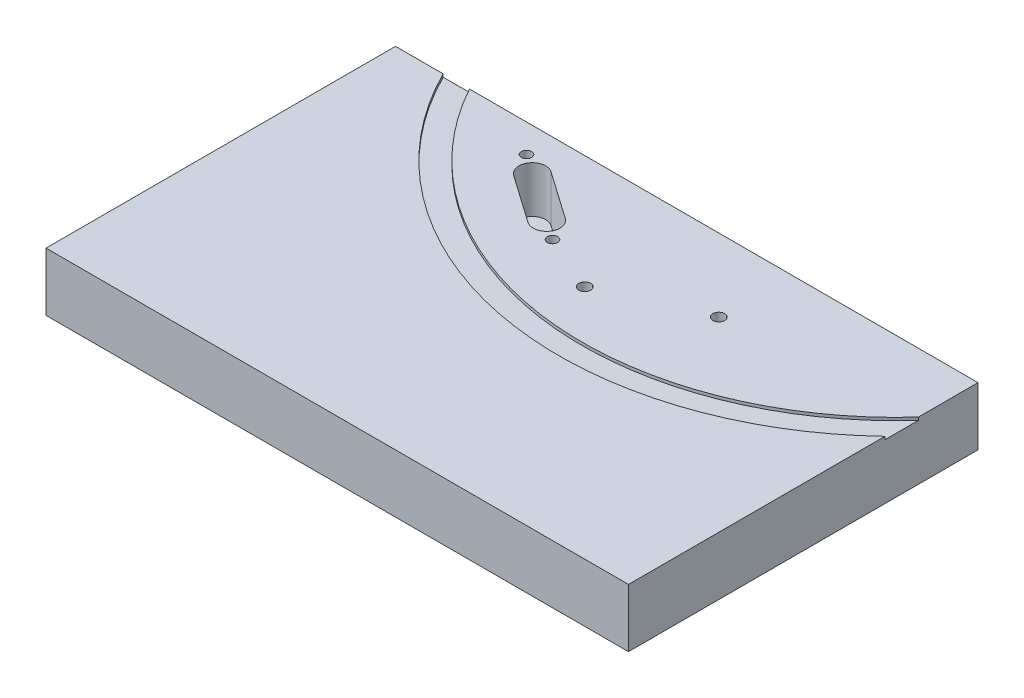
SolidWorks part; units mm, degrees
material "1060 Alloy"
ref_plane "Front Plane" through (0, 0, 0) normal (0, 0, 1) x (1, 0, 0)
ref_plane "Top Plane" through (0, 0, 0) normal (0, 1, 0) x (1, 0, 0)
ref_plane "Right Plane" through (0, 0, 0) normal (1, 0, 0) x (0, 0, -1)
ref_plane "Trap Symmetry Plane" through (60, 0, 0) normal (1, 0, 0) x (0, 0, -1)
ref_plane "Trap Centre Plane" through (0, 0, -26) normal (0, 0, 1) x (1, 0, 0)
ref_axis "Imaging Axis" through (60, 10.5, -26) along (0, -1, 0)
sketch "Sketch1" plane through (0, 0, 0) normal (0, 1, 0) x (1, 0, 0)
  line L1 (0, 0) -> (100, 0)
  line L2 (0, 0) -> (0, -60)
  line L3 (0, -60) -> (100, -60)
  line L4 (100, 0) -> (100, -60)
  dimension "D1" = 60
  dimension "D2" = 100
extrude "Boss-Extrude1" add sketch "Sketch1" along normal blind 10
hole_wizard "M2.5x0.45 Tapped Hole1" positions "Sketch2" profile "Sketch3" tap size "M2.5x0.45" standard "ANSI Metric"
sketch "Sketch2" plane through (0, 10, 0) normal (0, 1, 0) x (1, 0, 0)
  line L1 (52, -19.5) -> (68, -19.5)
  line L2 (52, -19.5) -> (52, -12.5)
  line L3 (52, -12.5) -> (68, -12.5)
  line L4 (68, -19.5) -> (68, -12.5)
  line L7 (60, -5.5) -> (60, 5.5) construction
  line L8 (100, 0) -> (0, 0) construction
  point P1 (52, -19.5)
  point P2 (68, -12.5)
  point P37 (60, -12.5)
  dimension "D1" = 7
  dimension "D2" = 16
  dimension "D3" = 12.5
sketch "Sketch3" plane through (52, 10, 19.5) normal (1, 0, 0) x (0, 0, 1)
  line L0 (0, 0) -> (0, 6.9659)
  line L1 (0, 6.9659) -> (1.025, 6.35)
  line L2 (1.025, 6.35) -> (1.025, 0)
  line L5 (1.025, 0) -> (0, 0)
  line L10 (0, 6.9659) -> (-1.025, 6.35) construction
  line L11 (0, -6.35) -> (0, 107.95) construction
  dimension "Tap Drill Dia." = 2.05
  dimension "Tap Drill Depth" = 6.35
  dimension "Drill Angle" = 118
cosmetic thread "Hole Thread3" parameters "D1"=5, "D2"=2.5
cosmetic thread "Hole Thread4" parameters "D1"=5, "D2"=2.5
hole_wizard "#2-56 Tapped Hole1" positions "Sketch4" profile "Sketch5" tap size "#2-56" standard "ANSI Inch"
sketch "Sketch4" plane through (0, 10, 0) normal (0, 1, 0) x (1, 0, 0)
  line L0 (42.2009, -15.2511) -> (27.3243, -4.8343)
  line L3 (34.7626, -10.0427) -> (60, 26)
  line L6 (60, 26) -> (60, -18)
  point P1 (42.2009, -15.2511)
  point P2 (27.3243, -4.8343)
  dimension "D1" = 35
  dimension "D2" = 44
  dimension "D3" = 18.161
sketch "Sketch5" plane through (42.2009, 10, 15.2511) normal (1, 0, 0) x (0, 0, 1)
  line L0 (0, 0) -> (0, 6.2642)
  line L1 (0, 6.2642) -> (0.889, 5.73)
  line L2 (0.889, 5.73) -> (0.889, 0)
  line L5 (0.889, 0) -> (0, 0)
  line L10 (0, 6.2642) -> (-0.889, 5.73) construction
  line L11 (0, -6.35) -> (0, 107.95) construction
  dimension "Tap Drill Dia." = 1.778
  dimension "Tap Drill Depth" = 5.73
  dimension "Drill Angle" = 118
cosmetic thread "Hole Thread5" parameters "D1"=4.37, "D2"=2.1844
cosmetic thread "Hole Thread6" parameters "D1"=4.37, "D2"=2.1844
sketch "Sketch6" plane through (0, 10, 0) normal (0, 1, 0) x (1, 0, 0)
  line L0 (27.3243, -4.8343) -> (42.2009, -15.2511) construction
  line L1 (38.8584, -12.9106) -> (30.6669, -7.1748) construction
  line L2 (37.5392, -14.7946) -> (29.3477, -9.0589)
  line L3 (40.1776, -11.0265) -> (31.9861, -5.2908)
  circle A2 centre (42.2009, -15.2511) radius 0.889 construction
  circle A3 centre (27.3243, -4.8343) radius 0.889 construction
  circle A4 centre (42.2009, -15.2511) radius 0.889 construction
  circle A5 centre (27.3243, -4.8343) radius 0.889 construction
  arc A6 (37.5392, -14.7946) -> (40.1776, -11.0265) centre (38.8584, -12.9106) ccw
  arc A7 (31.9861, -5.2908) -> (29.3477, -9.0589) centre (30.6669, -7.1748) ccw
  point P8 (34.7626, -10.0427)
  dimension "D1" = 4.6
  dimension "D2" = 10
extrude "Cut-Extrude2" cut sketch "Sketch6" against normal blind 8
hole_wizard "M3x0.5 Tapped Hole2" positions "Sketch10" profile "Sketch11" tap size "M3x0.5" standard "ANSI Metric"
sketch "Sketch10" plane through (0, 0, 0) normal (0, 0, -1) x (-1, 0, 0)
  line L0 (-100, 5) -> (0, 5) construction
  line L1 (-100, 10) -> (-100, 0) construction
  line L2 (0, 10) -> (0, 0) construction
  line L3 (-60, 10.5) -> (-60, -0.5) construction
  point P11 (-70, 5)
  point P13 (-20, 5)
  dimension "D3" = 50
  dimension "D4" = 10
  dimension "D5" = 40
sketch "Sketch11" plane through (20, 5, 0) normal (1, 0, 0) x (0, 1, 0)
  line L0 (0, 0) -> (0, 8.2511)
  line L1 (0, 8.2511) -> (1.25, 7.5)
  line L2 (1.25, 7.5) -> (1.25, 0)
  line L5 (1.25, 0) -> (0, 0)
  line L10 (0, 8.2511) -> (-1.25, 7.5) construction
  line L11 (0, -6.35) -> (0, 107.95) construction
  dimension "Tap Drill Dia." = 2.5
  dimension "Tap Drill Depth" = 7.5
  dimension "Drill Angle" = 118
cosmetic thread "Hole Thread7" parameters "D1"=6, "D2"=3
cosmetic thread "Hole Thread8" parameters "D1"=6, "D2"=3
sketch "Sketch12" plane through (0, 10, 0) normal (0, 1, 0) x (1, 0, 0)
  line L2 (100, 0) -> (0, 0) construction
  line L4 (100, -60) -> (100, 0) construction
  arc A0 (100, -10.2395) -> (11.7572, 1.7939) centre (60, 26) cw
  arc A1 (102.9643, -12.9251) -> (8.182, 0) centre (60, 26) cw
  arc A2 (100, -10.2395) -> (102.9643, -12.9251) centre (101.4822, -11.5823) cw
  arc A3 (11.7572, 1.7939) -> (8.182, 0) centre (9.9696, 0.8969) ccw
  dimension "D1" = 53.975
  dimension "D2" = 4
extrude "Cut-Extrude3" cut sketch "Sketch12" against normal blind 0.5
